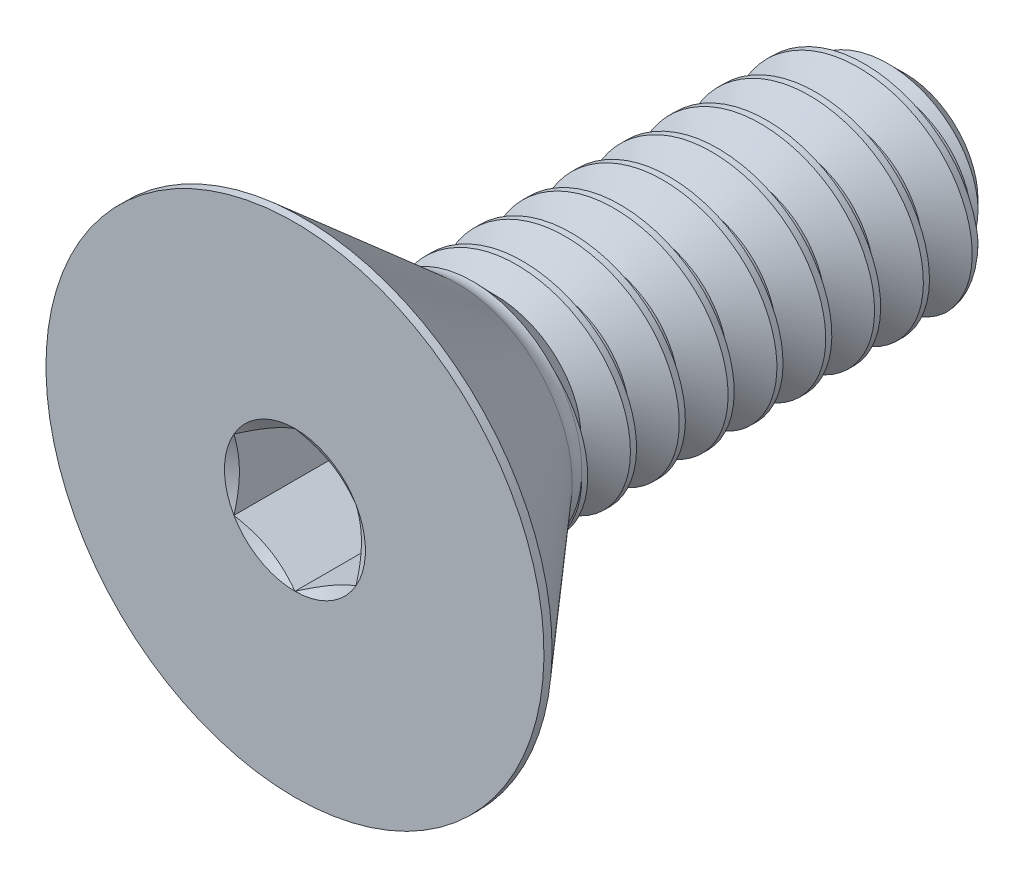
SolidWorks part; units mm, degrees
ref_plane "Front" through (0, 0, 0) normal (0, 0, 1) x (1, 0, 0)
ref_plane "Top" through (0, 0, 0) normal (0, 1, 0) x (1, 0, 0)
ref_plane "Right" through (0, 0, 0) normal (1, 0, 0) x (0, 0, -1)
sketch "Sketch1" plane through (0, 0, 0) normal (1, 0, 0) x (0, 0, -1)
  line L0 (0, 3.2385) -> (0.1054, 3.2385) construction
  line L1 (0.1054, 3.2385) -> (2.1082, 1.4975) construction
  line L2 (0, 1.4224) -> (7.9375, 1.4224)
  line L3 (7.9375, 1.4224) -> (7.9375, 0)
  line L4 (7.9375, 0) -> (0, 0)
  line L5 (0, 0) -> (0, 3.2385) construction
  line L6 (0, 3.2385) -> (0, -3.2385) construction
  line L7 (7.9375, 1.4224) -> (7.9375, -1.4224) construction
  line L8 (0, -3.2385) -> (0.1054, -3.2385) construction
  line L9 (0.1054, -3.2385) -> (2.1082, -1.4975) construction
  line L11 (0, 1.4224) -> (0, 0)
  line L12 (2.3091, 1.4224) -> (2.3091, 0) construction
  line L13 (-17.4625, 0) -> (-17.4625, 1.4224) construction
  arc A1 (2.1082, 1.4975) -> (2.3091, 1.4224) centre (2.3091, 1.7286) ccw construction
  dimension "D1" = 0.1054
  dimension "Min Thread" = 25.4
revolve "Revolve1" add sketch "Sketch1" angle 360 mid plane about L4
sketch "Sketch3" plane through (0, 0, -7.9375) normal (0, 0, -1) x (-1, 0, 0)
  circle A0 centre (0, 0) radius 1.4224
curve "Helix/Spiral1" pitch 0.635 height 7.9375 radius 1.4224 centre (0, 0, -7.9375) axis (0, 0, 1) start towards (0, 1, 0)
sketch "Sketch2" plane through (0, 0, 0) normal (1, 0, 0) x (0, 0, -1)
  line L0 (7.9375, 1.4224) -> (8.4931, 1.4224)
  line L1 (8.4931, 1.4224) -> (8.255, 1.01)
  line L2 (8.255, 1.01) -> (8.1756, 1.01)
  line L3 (8.1756, 1.01) -> (7.9375, 1.4224)
  line L4 (8.0566, 1.2162) -> (8.3741, 1.2162) construction
  dimension "D1" = 60
  dimension "D2" = 0.0794
  dimension "D3" = 0.3175
ref_plane "Plane2" through (0, 0, 17.4625) normal (0, 0, 1) x (1, 0, 0)
chamfer "Chamfer1" distance 0.4763 angle 45 1 edges at (-1.4224, 0, -7.9375)
sweep "Cut-Sweep1" cut profiles "Sketch2" path "Helix/Spiral1" align with end faces yes
sketch "Sketch7" plane through (0, 0, 0) normal (1, 0, 0) x (0, 0, -1)
  line L0 (0, 3.2385) -> (0.1054, 3.2385) construction
  line L1 (0.1054, 3.2385) -> (2.1082, 1.4975) construction
  line L2 (0, 3.2385) -> (0.1054, 3.2385)
  line L3 (0.1054, 3.2385) -> (2.1082, 1.4975)
  line L4 (2.3091, 1.4224) -> (2.3091, 0) construction
  line L5 (2.3091, 1.4224) -> (2.3091, 0)
  line L7 (0, 0) -> (0, 3.2385) construction
  line L8 (0, 0) -> (0, 3.2385)
  line L9 (0, 0) -> (2.3091, 0)
  line L10 (5.7417, 0) -> (-5.7417, 0) construction
  arc A0 (2.1082, 1.4975) -> (2.3091, 1.4224) centre (2.3091, 1.7286) ccw construction
  arc A1 (2.1082, 1.4975) -> (2.3091, 1.4224) centre (2.3091, 1.7286) ccw
revolve "Revolve2" add sketch "Sketch7" angle 360 mid plane about L9
ref_plane "Plane1" through (0, 0, -2.3091) normal (0, 0, 1) x (1, 0, 0)
sketch "Sketch8" plane through (0, 0, -2.3091) normal (0, 0, 1) x (1, 0, 0)
  circle A0 centre (0, 0) radius 1.4224
extrude "Boss-Extrude1" add sketch "Sketch8" against normal through all draft 46
sketch "Sketch5" plane through (0, 0, 0) normal (0, 0, 1) x (1, 0, 0)
  line L0 (0, 0) -> (-0.9165, 0) construction
  line L1 (0, 0) -> (-2.7496, 1.5875) construction
  line L2 (0, 0) -> (-2.7496, -1.5875) construction
  line L6 (0, 0.9165) -> (0, 0.7559) construction
  line L7 (0, 0.7559) -> (0, 0.5953) construction
  line L9 (0, 0.9165) -> (-0.7937, 0.4583)
  line L10 (-0.7937, 0.4583) -> (-0.7937, -0.4583)
  line L11 (-0.7937, -0.4583) -> (0, -0.9165)
  line L12 (0, -0.9165) -> (0.7937, -0.4583)
  line L13 (0.7937, -0.4583) -> (0.7938, 0.4583)
  line L14 (0.7938, 0.4583) -> (0, 0.9165)
  circle A0 centre (0, 0) radius 0.9165 construction
  circle A1 centre (0, 0) radius 0.7559 construction
  circle A2 centre (0, 0) radius 0.5953 construction
  circle A3 centre (0, 0) radius 0.7938 construction
  dimension "D3" = 1.1906
  dimension "D4" = 30
  dimension "D5" = 30
  dimension "Hex" = 1.5875
extrude "Cut-Extrude2" cut sketch "Sketch5" against normal blind 1.4757
sketch "Sketch6" plane through (0, 0, 0) normal (0, 0, 1) x (1, 0, 0)
  circle A0 centre (0, 0) radius 0.9165
extrude "Cut-Extrude3" cut sketch "Sketch6" against normal blind 1.4757 draft 60
sketch "Sketch9" [suppressed] plane through (0, 0, -3.6076) normal (0, 0, 1) x (1, 0, 0)
  circle A1 centre (0, 0) radius 2.413
  circle A2 centre (0, 0) radius 2.413
  point P0 (0, 2.413)
  dimension "D1" = 0
extrude "Boss-Extrude2" [suppressed] add sketch "Sketch9" against normal up to surface (15.4424 mm away) up to plane "Plane2"
sketch "Sketch10" plane through (0, 0, 0) normal (1, 0, 0) x (0, 0, -1)
  line L0 (7.9375, 1.4224) -> (7.9375, -1.4224) construction
  point P0 (6.985, -1.4224)
  dimension "D1" = 0.9525
equation "\"D3@Helix/Spiral1\" = \"Lg@Sketch1\""
equation "\"D2@Sketch2\" = \"D4@Helix/Spiral1\" * .125"
equation "\"D3@Sketch2\" = \"D4@Helix/Spiral1\" * .5"
equation "\"D1@Chamfer1\" = \"D4@Helix/Spiral1\" * .75"
equation "\"D1@Cut-Extrude2\" = \"Head Ht@Sketch1\" * .7"
equation "\"D1@Sketch1\" = \"Head Ht@Sketch1\" * .05"
equation "\"D1@Sketch10\" = \"D4@Helix/Spiral1\" * 1.5"
equation "\"D1@Cut-Extrude3\" = \"D1@Cut-Extrude2\""
equation "\"D3@Sketch5\" = \"Hex@Sketch5\" * .75"
